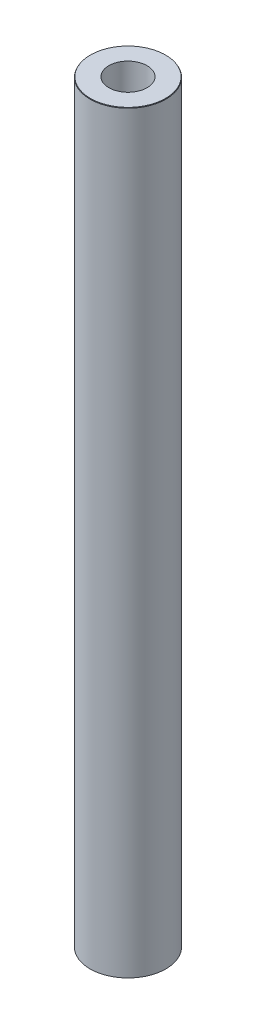
SolidWorks part; units mm, degrees
ref_plane "Front Plane" through (0, 0, 0) normal (0, 0, 1) x (1, 0, 0)
ref_plane "Top Plane" through (0, 0, 0) normal (0, 1, 0) x (1, 0, 0)
ref_plane "Right Plane" through (0, 0, 0) normal (1, 0, 0) x (0, 0, -1)
sketch "Sketch1" plane through (0, 0, 0) normal (0, 1, 0) x (1, 0, 0)
  circle A0 centre (0, 0) radius 15
  dimension "SHAFT_OD" = 30
extrude "Boss-Extrude1" add sketch "Sketch1" along normal blind 298.3945
sketch "Sketch2" plane through (0, 0, 0) normal (0, 1, 0) x (1, 0, 0)
  circle A0 centre (0, 0) radius 7.5698
  dimension "BORE_D" = 15.1397
extrude "Cut-Extrude1" cut sketch "Sketch2" along normal through all
chamfer "Chamfer1" distance 0.219 angle 29.963 2 edges at (0, 298.3945, 15) (0, 0, 15) first distance on face at (0, 298.3945, 15) first distance on face at (0, 0, 7.5698)
